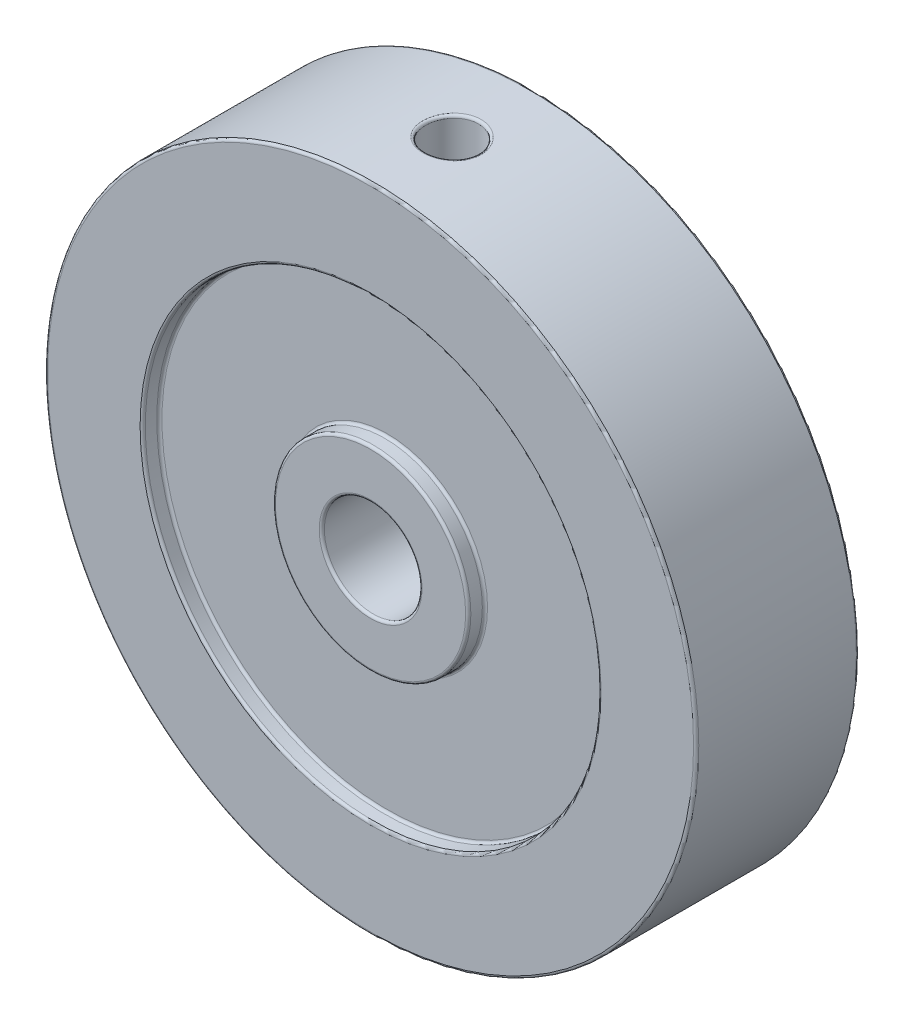
SolidWorks part; units mm, degrees
material "AISI 1020"
ref_plane "Front Plane" through (0, 0, 0) normal (0, 0, 1) x (1, 0, 0)
ref_plane "Top Plane" through (0, 0, 0) normal (0, 1, 0) x (1, 0, 0)
ref_plane "Right Plane" through (0, 0, 0) normal (1, 0, 0) x (0, 0, -1)
sketch "Sketch1" plane through (0, 0, 0) normal (0, 0, 1) x (1, 0, 0)
  circle A0 centre (0, 0) radius 15.875
  dimension "D1" = 31.75
extrude "Boss-Extrude1" add sketch "Sketch1" along normal mid plane 7.9375 contours A0
sketch "Sketch2" plane through (0, 0, 3.9688) normal (0, 0, 1) x (1, 0, 0)
  circle A0 centre (0, 0) radius 2.3813
  circle A1 centre (0, 0) radius 4.7625
  circle A2 centre (0, 0) radius 11.1125
  dimension "D1" = 4.7625
  dimension "D2" = 22.225
  dimension "D3" = 9.525
extrude "Cut-Extrude1" cut sketch "Sketch2" against normal through all contours A0 region at (0, 0, 3.9688)
extrude "Cut-Extrude2" cut sketch "Sketch2<3>" against normal blind 0.8128 contours A2 A1 region at (-10.7982, 0, 3.9688)
sketch "Sketch2<3>" plane through (0, 0, 3.9688) normal (0, 0, 1) x (1, 0, 0) same geometry as "Sketch2"
mirror "Mirror2" about plane through (0, 0, 0) normal (0, 0, 1) of "Cut-Extrude2"
ref_plane "Plane1" through (0, 15.875, 0) normal (0, 1, 0) x (1, 0, 0)
hole_wizard "#5-40 Tapped Hole1" positions "Sketch5" profile "Sketch6" tap size "#5-40" standard "ANSI Inch"
sketch "Sketch5" plane through (0, 15.875, 0) normal (0, 1, 0) x (1, 0, 0)
  point P0 (0, 0)
sketch "Sketch6" plane through (0, 15.875, 0) normal (1, 0, 0) x (0, 0, 1)
  line L0 (0, 0) -> (0, 17.2845)
  line L1 (0, 17.2845) -> (1.289, 16.51)
  line L2 (1.289, 16.51) -> (1.289, 0)
  line L5 (1.289, 0) -> (0, 0)
  line L10 (0, 17.2845) -> (-1.2891, 16.51) construction
  line L11 (0, -6.35) -> (0, 107.95) construction
  dimension "Tap Drill Dia." = 2.5781
  dimension "Tap Drill Depth" = 16.51
  dimension "Drill Angle" = 118
cosmetic thread "Hole Thread1" parameters "D1"=6.35, "D2"=3.175
fillet "Fillet1" radius 0.127 13 edges at (4.7625, 0, -3.9688) (2.3813, 0, -3.9688) (11.1125, 0, -3.156) (4.7625, 0, -3.156) (11.1125, 0, -3.9688) (4.7625, 0, 3.9688) (2.3813, 0, 3.9688) (11.1125, 0, 3.156) (4.7625, 0, 3.156) (11.1125, 0, 3.9688) (15.875, 0, -3.9688) (15.875, 0, 3.9688) (0.2917, 15.8723, -1.2556)
